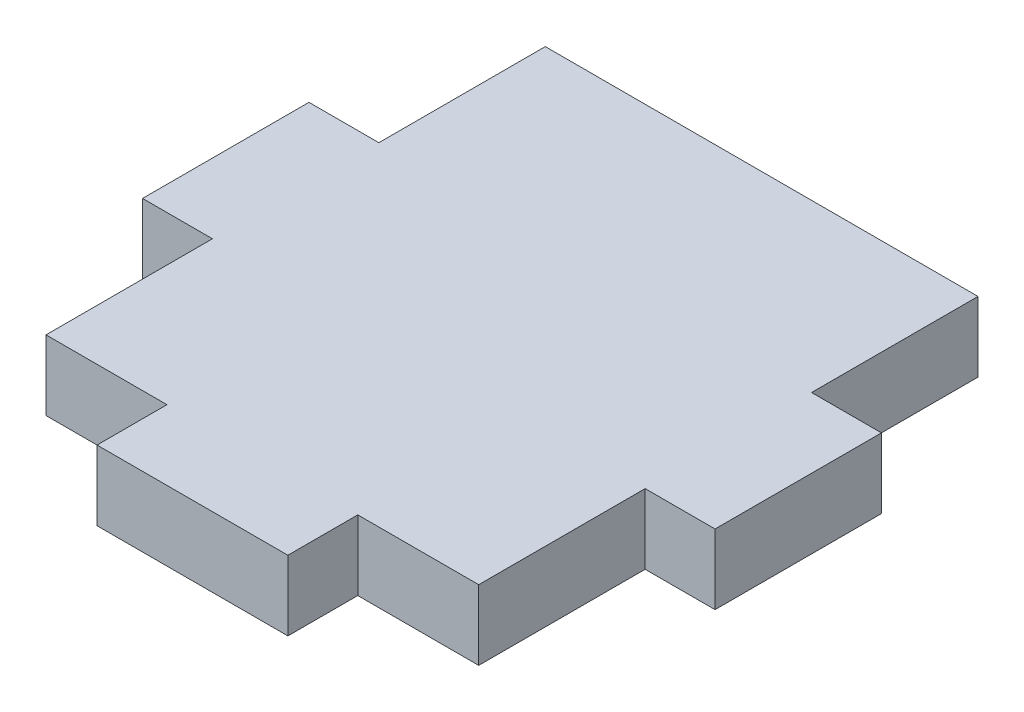
SolidWorks part; units mm, degrees
ref_plane "Front Plane" through (0, 0, 0) normal (0, 0, 1) x (1, 0, 0)
ref_plane "Top Plane" through (0, 0, 0) normal (0, 1, 0) x (1, 0, 0)
ref_plane "Right Plane" through (0, 0, 0) normal (1, 0, 0) x (0, 0, -1)
sketch "Sketch1" plane through (0, 0, 0) normal (0, 1, 0) x (1, 0, 0)
  line L1 (-16.51, -19.05) -> (16.51, -19.05)
  line L2 (-16.51, -19.05) -> (-16.51, 19.05)
  line L3 (-16.51, 19.05) -> (16.51, 19.05)
  line L4 (16.51, -19.05) -> (16.51, 19.05)
  line L5 (-16.51, -19.05) -> (16.51, 19.05) construction
  line L6 (-16.51, 19.05) -> (16.51, -19.05) construction
  point P0 (0, 0)
  dimension "D1" = 38.1
  dimension "D2" = 33.02
extrude "Boss-Extrude1" add sketch "Sketch1" along normal mid plane 5.334
sketch "Sketch2" plane through (0, 2.667, 0) normal (0, 1, 0) x (1, 0, 0)
  line L0 (-16.51, -19.05) -> (16.51, -19.05) construction
  line L1 (-7.2813, -19.05) -> (7.2813, -19.05)
  line L2 (-7.2813, -19.05) -> (-7.2813, -24.384)
  line L3 (-7.2813, -24.384) -> (7.2813, -24.384)
  line L4 (7.2813, -19.05) -> (7.2813, -24.384)
  line L5 (-21.844, -6.35) -> (-21.844, -19.05) construction
  line L6 (7.2813, -19.05) -> (21.844, -19.05) construction
  line L7 (-16.51, 19.05) -> (-16.51, -19.05) construction
  line L8 (-16.51, -6.35) -> (-21.844, -6.35)
  line L9 (-16.51, -6.35) -> (-16.51, 6.35)
  line L10 (-16.51, 6.35) -> (-21.844, 6.35)
  line L11 (-21.844, -6.35) -> (-21.844, 6.35)
  line L12 (-16.51, 19.05) -> (-16.51, 6.35) construction
  line L13 (-16.51, -6.35) -> (-16.51, -19.05) construction
  line L14 (0, 19.05) -> (0, -19.05) construction
  line L15 (16.51, 19.05) -> (-16.51, 19.05) construction
  line L16 (21.844, -6.35) -> (21.844, 6.35)
  line L17 (16.51, 6.35) -> (21.844, 6.35)
  line L18 (16.51, -6.35) -> (16.51, 6.35)
  line L19 (16.51, -6.35) -> (21.844, -6.35)
  line L20 (21.844, -19.05) -> (21.844, -6.35) construction
  line L21 (-21.844, -19.05) -> (-16.51, -19.05) construction
  dimension "D1" = 5.334
  dimension "D2" = 5.334
extrude "Boss-Extrude2" add sketch "Sketch2" against normal blind 5.334
equation "\"D1@Boss-Extrude1\"=\"material\""
equation "\"D1@Boss-Extrude2\"=\"material\""
equation "\"material\"=\"GMaterial@Platform.assembly\""
